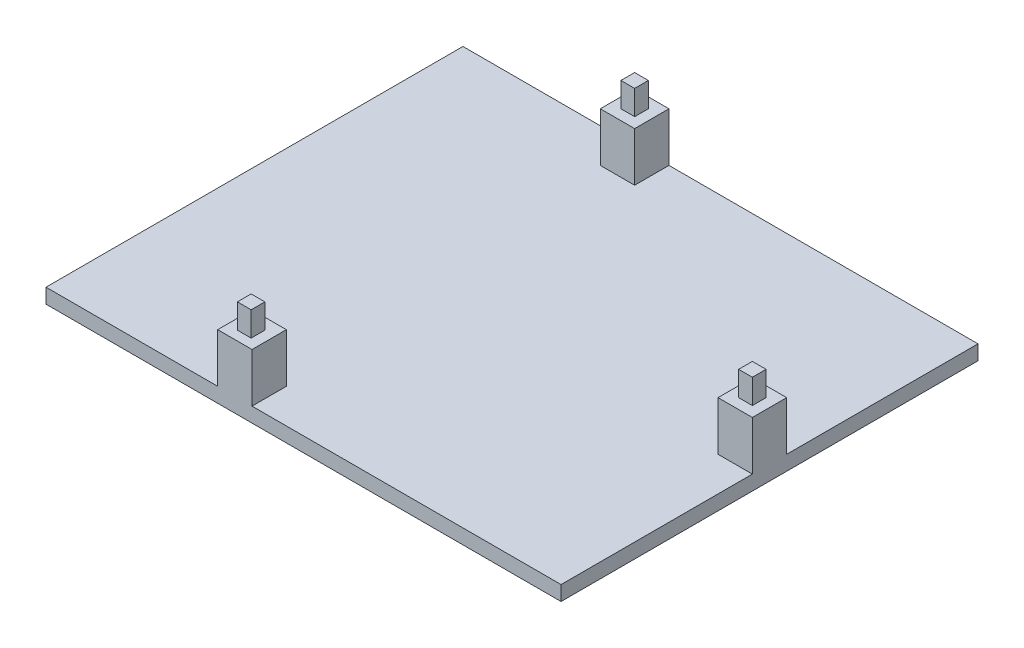
SolidWorks part; units mm, degrees
ref_plane "Front Plane" through (0, 0, 0) normal (0, 0, 1) x (1, 0, 0)
ref_plane "Top Plane" through (0, 0, 0) normal (0, 1, 0) x (1, 0, 0)
ref_plane "Right Plane" through (0, 0, 0) normal (1, 0, 0) x (0, 0, -1)
sketch "Sketch1" plane through (0, 0, 0) normal (0, 1, 0) x (1, 0, 0)
  line L0 (-62.7902, 25.249) -> (42.2098, 25.249)
  line L1 (42.2098, 25.249) -> (42.2098, -59.751)
  line L2 (42.2098, -59.751) -> (-62.7902, -59.751)
  line L3 (-62.7902, -59.751) -> (-62.7902, 25.249)
extrude "Boss-Extrude1" add sketch "Sketch1" along normal blind 3
sketch "Sketch2" plane through (0, 3, 0) normal (0, 1, 0) x (1, 0, 0)
  line L0 (-62.7902, -59.751) -> (-27.7902, -59.751)
  line L1 (-62.7902, -59.751) -> (42.2098, -59.751) construction
  line L2 (-27.7902, -59.751) -> (-27.7902, -52.751)
  line L3 (-27.7902, -52.751) -> (-20.7902, -52.751)
  line L4 (-20.7902, -52.751) -> (-20.7902, -59.751)
  line L5 (-20.7902, -59.751) -> (-27.7902, -59.751)
  line L8 (-25.6902, -55.0309) -> (-25.6902, -57.8309)
  line L9 (-25.6902, -55.0309) -> (-22.8902, -55.0309)
  line L10 (-22.8902, -55.0309) -> (-22.8902, -57.8309)
  line L11 (-22.8902, -57.8309) -> (-25.6902, -57.8309)
  point P5 (0, 0)
  line M14 (-62.7902, -59.751) -> (42.2098, -59.751)
extrude "Boss-Extrude2" add sketch "Sketch2" along normal blind 15 contours L9 L10 L11 L8
extrude "Boss-Extrude3" add sketch "Sketch2<7>" along normal blind 10 contours L4 L3 L2 L10 L11 L8 L9 M14 region at (-27.6913, 3, 56.251)
sketch "Sketch2<7>" plane through (0, 3, 0) normal (0, 1, 0) x (1, 0, 0) same geometry as "Sketch2"
sketch "Sketch4" plane through (0, 3, 0) normal (0, 1, 0) x (1, 0, 0)
  line L0 (-62.7902, 25.249) -> (-27.7902, 25.249)
  line L1 (42.2098, 25.249) -> (-62.7902, 25.249) construction
  line L2 (-27.7902, 25.249) -> (-27.7902, 18.249)
  line L3 (-27.7902, 18.249) -> (-20.7902, 18.249)
  line L4 (-20.7902, 18.249) -> (-20.7902, 25.249)
  line L5 (-20.7902, 25.249) -> (-27.7902, 25.249)
  line L8 (-25.6902, 20.349) -> (-22.8902, 20.349)
  line L9 (-22.8902, 20.349) -> (-22.8902, 23.149)
  line L10 (-25.6902, 20.349) -> (-25.6902, 23.149)
  line L11 (-25.6902, 23.149) -> (-22.8902, 23.149)
extrude "Boss-Extrude7" add sketch "Sketch4" along normal blind 15 contours L10 L11 L9 L8
sketch "Sketch8" plane through (0, 3, 0) normal (0, 1, 0) x (1, 0, 0)
  line L0 (-62.7902, 25.249) -> (-27.7902, 25.249)
  line L1 (42.2098, 25.249) -> (-62.7902, 25.249) construction
  line L2 (-27.7902, 25.249) -> (-27.7902, 18.249)
  line L3 (-27.7902, 18.249) -> (-20.7902, 18.249)
  line L4 (-20.7902, 18.249) -> (-20.7902, 25.249)
  line L5 (-20.7902, 25.249) -> (-27.7902, 25.249)
  line M8 (42.2098, 25.249) -> (-62.7902, 25.249)
  line M12 (-22.8902, 20.349) -> (-25.6902, 20.349)
  line M13 (-25.6902, 20.349) -> (-25.6902, 23.149)
  line M14 (-25.6902, 23.149) -> (-22.8902, 23.149)
  line M15 (-22.8902, 23.149) -> (-22.8902, 20.349)
extrude "Boss-Extrude8" add sketch "Sketch8" along normal blind 10 contours L3 L4 L2 M8 M15 M12 M13 M14 region at (-24.2902, 3, -25.15)
sketch "Sketch9" plane through (0, 3, 0) normal (0, 1, 0) x (1, 0, 0)
  line L0 (42.2098, -59.751) -> (42.2098, -20.751)
  line L1 (42.2098, -59.751) -> (42.2098, 25.249) construction
  line L2 (42.2098, -20.751) -> (35.2098, -20.751)
  line L3 (35.2098, -20.751) -> (35.2098, -13.751)
  line L4 (35.2098, -13.751) -> (42.2098, -13.751)
  line L5 (42.2098, -13.751) -> (42.2098, -20.751)
  line L8 (37.3098, -18.651) -> (37.3098, -15.851)
  line L9 (37.3098, -15.851) -> (40.1098, -15.851)
  line L10 (40.1098, -15.851) -> (40.1098, -18.651)
  line L11 (40.1098, -18.651) -> (37.3098, -18.651)
extrude "Boss-Extrude9" add sketch "Sketch9" along normal blind 15 contours L8 L9 L10 L11
sketch "Sketch10" plane through (0, 3, 0) normal (0, 1, 0) x (1, 0, 0)
  line L0 (42.2098, -59.751) -> (42.2098, -20.751)
  line L1 (42.2098, -59.751) -> (42.2098, 25.249) construction
  line L2 (42.2098, -20.751) -> (35.2098, -20.751)
  line L3 (35.2098, -20.751) -> (35.2098, -13.751)
  line L4 (35.2098, -13.751) -> (42.2098, -13.751)
  line L5 (42.2098, -13.751) -> (42.2098, -20.751)
  line M4 (40.1098, -15.851) -> (40.1098, -18.651)
  line M5 (40.1098, -18.651) -> (37.3098, -18.651)
  line M6 (37.3098, -18.651) -> (37.3098, -15.851)
  line M7 (37.3098, -15.851) -> (40.1098, -15.851)
  line M18 (42.2098, -59.751) -> (42.2098, 25.249)
extrude "Boss-Extrude10" add sketch "Sketch10" along normal blind 10 contours L4 L3 L2 M18 M7 M4 M5 M6 region at (38.7098, 3, 20.652)
